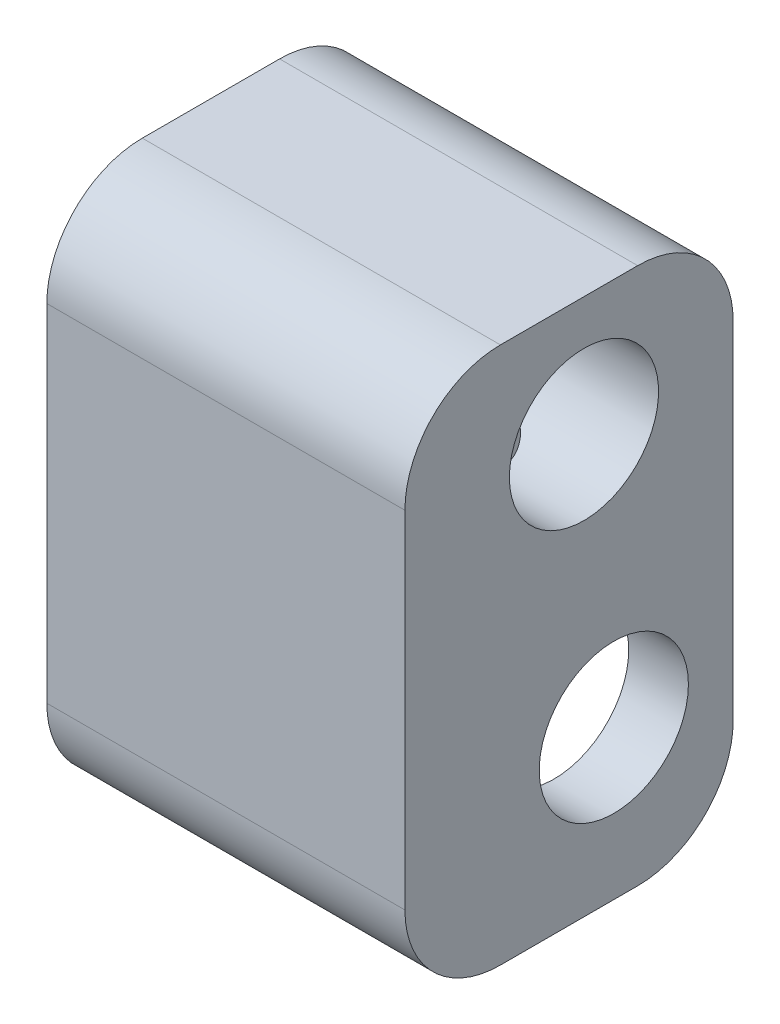
SolidWorks part; units mm, degrees
material "1060 Alloy"
ref_plane "Front Plane" through (0, 0, 0) normal (0, 0, 1) x (1, 0, 0)
ref_plane "Top Plane" through (0, 0, 0) normal (0, 1, 0) x (1, 0, 0)
ref_plane "Right Plane" through (0, 0, 0) normal (1, 0, 0) x (0, 0, -1)
sketch "Sketch1" plane through (0, 0, 0) normal (1, 0, 0) x (0, 0, -1)
  line L1 (0, 0) -> (5.5, 0)
  line L2 (0, 0) -> (0, 9)
  line L3 (0, 9) -> (5.5, 9)
  line L4 (5.5, 0) -> (5.5, 9)
  circle A0 centre (3.5, 2.5) radius 1.25
  dimension "D1" = 2.5
  dimension "D2" = 9
  dimension "D3" = 2.5
  dimension "D4" = 2
  dimension "D5" = 5.5
extrude "Boss-Extrude1" add sketch "Sketch1" along normal blind 6
sketch "Sketch4" plane through (0, 0, -5.5) normal (0, 0, -1) x (-1, 0, 0)
  line L0 (-3.75, 0) -> (-3.75, 4.8) construction
  line L1 (-6, 0) -> (0, 0) construction
  line L2 (-5, 0) -> (-5, 4.8)
  line L3 (-2.5, 0) -> (-2.5, 4.8)
  line L4 (-6, 0) -> (-6, 9) construction
  arc A0 (-5, 0) -> (-2.5, 0) centre (-3.75, 0) ccw
  arc A1 (-2.5, 4.8) -> (-5, 4.8) centre (-3.75, 4.8) ccw
  point P4 (-3.75, 2.4)
  dimension "D1" = 2.5
  dimension "D2" = 1
  dimension "D3" = 4.8
extrude "Cut-Extrude3" cut sketch "Sketch4" against normal blind 4.5
sketch "Sketch5" plane through (0, 0, 0) normal (-1, 0, 0) x (0, 0, 1)
  line L0 (-5.5, 9) -> (0, 9) construction
  line L2 (-5.5, 0) -> (-5.5, 9) construction
  circle A0 centre (-3, 7) radius 1.25
  dimension "D1" = 2.5
  dimension "D2" = 2
  dimension "D3" = 2.5
extrude "Cut-Extrude4" cut sketch "Sketch5" against normal up to next
fillet "Fillet1" radius 1.6 5 edges at (3, 0, 0) (3, 9, 0) (5.5, 0, -5.5) (1.25, 0, -5.5) (3, 9, -5.5)
